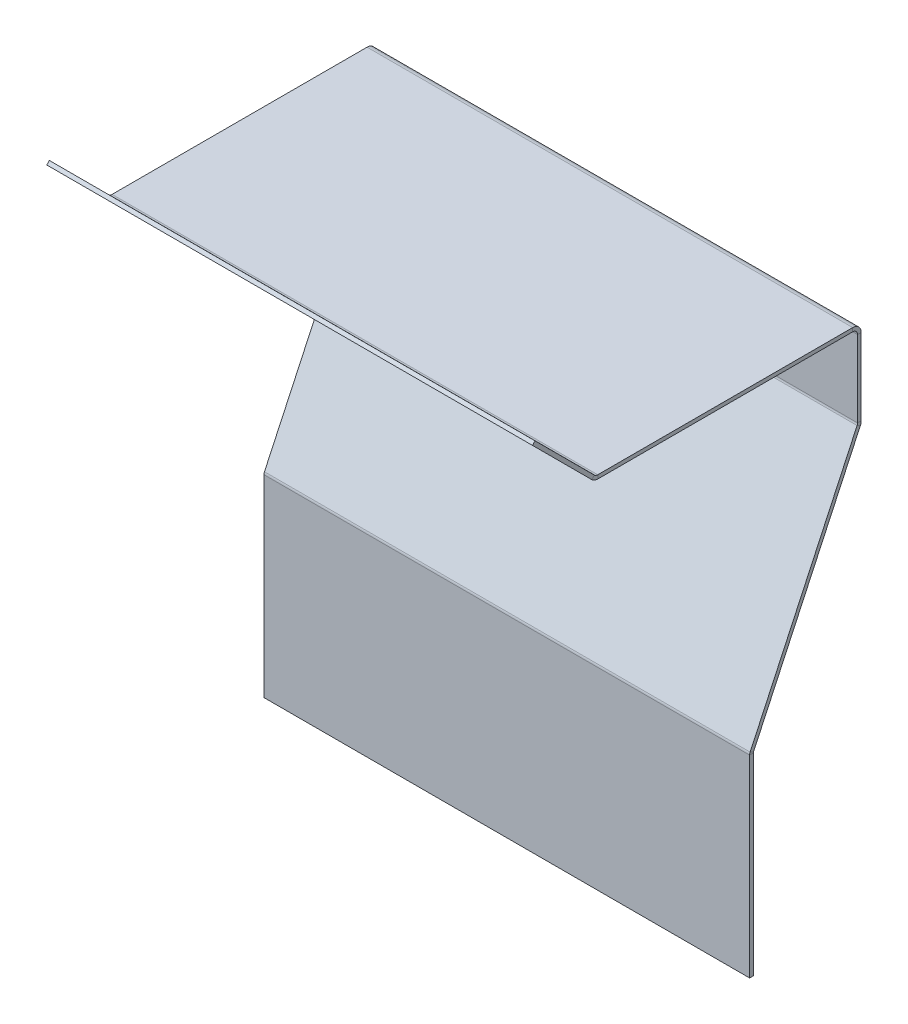
SolidWorks part; units mm, degrees
note: The reader was unsure of these and kept them because the rebuilt part matched: flange length of "Edge-Flange1", "Edge-Flange2", "Edge-Flange3", "Edge-Flange4".
ref_plane "Front Plane" through (0, 0, 0) normal (0, 0, 1) x (1, 0, 0)
ref_plane "Top Plane" through (0, 0, 0) normal (0, 1, 0) x (1, 0, 0)
ref_plane "Right Plane" through (0, 0, 0) normal (1, 0, 0) x (0, 0, -1)
sketch "Sketch1" plane through (0, 0, 0) normal (0, 1, 0) x (1, 0, 0)
  line L1 (-100, -52.5) -> (100, -52.5)
  line L2 (-100, -52.5) -> (-100, 52.5)
  line L3 (-100, 52.5) -> (100, 52.5)
  line L4 (100, -52.5) -> (100, 52.5)
  line L5 (-100, -52.5) -> (100, 52.5) construction
  line L6 (-100, 52.5) -> (100, -52.5) construction
  point P0 (0, 0)
  dimension "D1" = 200
  dimension "D2" = 105
base flange "Base-Flange1" sketch "Sketch1" thickness 1.524 reverse thickness direction no parameters "D1"=0.7366
edge flange "Edge-Flange1" sketch "Sketch8" flange angle 135 flange length 36 flange position bend outside bend radius 1.9812 thickness 1.524 parameters "D6"=10
sketch "Sketch8" plane through (0, 0, 52.5) normal (0, -0.7071, 0.7071) x (1, 0, 0)
  line L2 (-100, 0) -> (-100, 35.3687)
  line L3 (-100, 35.3687) -> (100, 35.3687)
  line L4 (100, 35.3687) -> (100, 0)
  line L7 (-100, 0) -> (100, 0) construction
  line L8 (-100, 0) -> (100, 0)
bend "EdgeBend1" bend radius 1.9812 bend angle 45 parameters "D5"=1
edge flange "Edge-Flange2" sketch "Sketch11" flange angle 90 flange length 35 flange position bend outside bend radius 1.9812 thickness 1.524 parameters "D6"=10
sketch "Sketch11" plane through (0, -1.524, -52.5) normal (0, 0, -1) x (1, 0, 0)
  line L0 (100, 0) -> (-100, 0) construction
  line L1 (100, 0) -> (-100, 0)
  line L2 (-100, 0) -> (-100, 33.476)
  line L3 (-100, 33.476) -> (100, 33.476)
  line L4 (100, 33.476) -> (100, 0)
bend "EdgeBend2" bend radius 1.9812 bend angle 90 parameters "D5"=2
edge flange "Edge-Flange3" sketch "Sketch14" flange angle 155 flange length 105 flange position bend outside bend radius 1.9812 thickness 1.524 parameters "D6"=10
sketch "Sketch14" plane through (0, -35, -54.4812) normal (0, -0.4226, -0.9063) x (1, 0, 0)
  line L2 (-100, 0) -> (-100, 104.6621)
  line L3 (-100, 104.6621) -> (100, 104.6621)
  line L4 (100, 104.6621) -> (100, 0)
  line L15 (100, 0) -> (-100, 0) construction
  line L16 (100, 0) -> (-100, 0)
bend "EdgeBend3" bend radius 1.9812 bend angle 25 parameters "D5"=3
edge flange "Edge-Flange4" sketch "Sketch17" flange angle 155 flange length 80 flange position bend outside bend radius 0.7366 thickness 1.524 parameters "D6"=10
sketch "Sketch17" plane through (0, -130.9394, -11.6303) normal (0, 0, 1) x (-1, 0, 0)
  line L2 (-100, 0) -> (-100, 79.6621)
  line L3 (-100, 79.6621) -> (100, 79.6621)
  line L4 (100, 79.6621) -> (100, 0)
  line L39 (-100, 0) -> (100, 0) construction
  line L40 (-100, 0) -> (100, 0)
bend "EdgeBend4" bend radius 0.7366 bend angle 25 parameters "D5"=4
sketch "Bend-Lines1" [suppressed] plane through (0, 0, 0) normal (0, 1, 0) x (1, 0, 0)
sketch "Bounding-Box1" [suppressed] plane through (0, 0, 0) normal (0, 1, 0) x (1, 0, 0)
sheet metal parameters "Sheet-Metal1" thickness 1.524 parameters "D1"=0.7366
flat pattern "Flat-Pattern1" [suppressed]
sketch "Bend-Lines2" plane through (0, 0, 0) normal (0, 1, 0) x (1, 0, 0)
sketch3d "Bounding-Box2" [suppressed]
  line L0 (100, 52.5, 0) -> (-100, 52.5, 0) construction
  line L1 (100, -52.5, 0) -> (-100, -52.5, 0) construction
  line L2 (100, 52.5, 0) -> (100, -52.5, 0) construction
  line L3 (-100, 52.5, 0) -> (-100, -52.5, 0) construction
sheet metal parameters "Sheet-Metal2" thickness 1.524 parameters "D1"=0.7366
flat pattern "Flat-Pattern1"
sketch "Bend-Lines2" plane through (0, 0, 0) normal (0, 1, 0) x (1, 0, 0)
  line L0 (-100, -53.5473) -> (100, -53.5473) construction
  line L1 (-100, -53.5473) -> (100, -53.5473) construction
sketch3d "Bounding-Box2" [suppressed]
  line L0 (100, 52.5, 0) -> (-100, 52.5, 0) construction
  line L1 (100, -89.1428, 0) -> (-100, -89.1428, 0) construction
  line L2 (100, 52.5, 0) -> (100, -89.1428, 0) construction
  line L3 (-100, 52.5, 0) -> (-100, -89.1428, 0) construction
bend of the flat pattern "Flatten-<EdgeBend1>1"
sheet metal parameters "Sheet-Metal3" thickness 1.524 parameters "D1"=0.7366
flat pattern "Flat-Pattern1"
sketch "Bend-Lines2" plane through (0, 0, 0) normal (0, 1, 0) x (1, 0, 0)
  line L0 (-100, -53.5473) -> (100, -53.5473) construction
  line L1 (-100, -53.5473) -> (100, -53.5473) construction
  line L2 (100, 54.5947) -> (-100, 54.5947) construction
  line L3 (100, 54.5947) -> (-100, 54.5947) construction
sketch3d "Bounding-Box2" [suppressed]
  line L0 (100, 88.1841, 0) -> (-100, 88.1841, 0) construction
  line L1 (100, -89.1428, 0) -> (-100, -89.1428, 0) construction
  line L2 (100, 88.1841, 0) -> (100, -89.1428, 0) construction
  line L3 (-100, 88.1841, 0) -> (-100, -89.1428, 0) construction
bend of the flat pattern "Flatten-<EdgeBend1>1"
bend of the flat pattern "Flatten-<EdgeBend2>1"
sheet metal parameters "Sheet-Metal4" thickness 1.524 parameters "D1"=0.7366
flat pattern "Flat-Pattern1"
sketch "Bend-Lines2" plane through (0, 0, 0) normal (0, 1, 0) x (1, 0, 0)
  line L0 (-100, -53.5473) -> (100, -53.5473) construction
  line L1 (-100, -53.5473) -> (100, -53.5473) construction
  line L2 (100, 54.5947) -> (-100, 54.5947) construction
  line L3 (100, 54.5947) -> (-100, 54.5947) construction
  line L4 (100, 88.766) -> (-100, 88.766) construction
  line L5 (100, 88.766) -> (-100, 88.766) construction
sketch3d "Bounding-Box2" [suppressed]
  line L0 (-100, -89.1428, 0) -> (-100, 193.5707, 0) construction
  line L1 (100, -89.1428, 0) -> (100, 193.5707, 0) construction
  line L2 (-100, -89.1428, 0) -> (100, -89.1428, 0) construction
  line L3 (-100, 193.5707, 0) -> (100, 193.5707, 0) construction
bend of the flat pattern "Flatten-<EdgeBend1>1"
bend of the flat pattern "Flatten-<EdgeBend2>1"
bend of the flat pattern "Flatten-<EdgeBend3>1"
sheet metal parameters "Sheet-Metal5" thickness 1.524 parameters "D1"=0.7366
flat pattern "Flat-Pattern1"
sketch "Bend-Lines2" plane through (0, 0, 0) normal (0, 1, 0) x (1, 0, 0)
  line L0 (-100, -53.5473) -> (100, -53.5473) construction
  line L1 (-100, -53.5473) -> (100, -53.5473) construction
  line L2 (100, 54.5947) -> (-100, 54.5947) construction
  line L3 (100, 54.5947) -> (-100, 54.5947) construction
  line L4 (100, 88.766) -> (-100, 88.766) construction
  line L5 (100, 88.766) -> (-100, 88.766) construction
  line L6 (100, 193.881) -> (-100, 193.881) construction
  line L7 (100, 193.881) -> (-100, 193.881) construction
sketch3d "Bounding-Box2" [suppressed]
  line L0 (-100, -89.1428, 0) -> (-100, 273.6902, 0) construction
  line L1 (100, -89.1428, 0) -> (100, 273.6902, 0) construction
  line L2 (-100, -89.1428, 0) -> (100, -89.1428, 0) construction
  line L3 (-100, 273.6902, 0) -> (100, 273.6902, 0) construction
bend of the flat pattern "Flatten-<EdgeBend1>1"
bend of the flat pattern "Flatten-<EdgeBend2>1"
bend of the flat pattern "Flatten-<EdgeBend3>1"
bend of the flat pattern "Flatten-<EdgeBend4>1"
